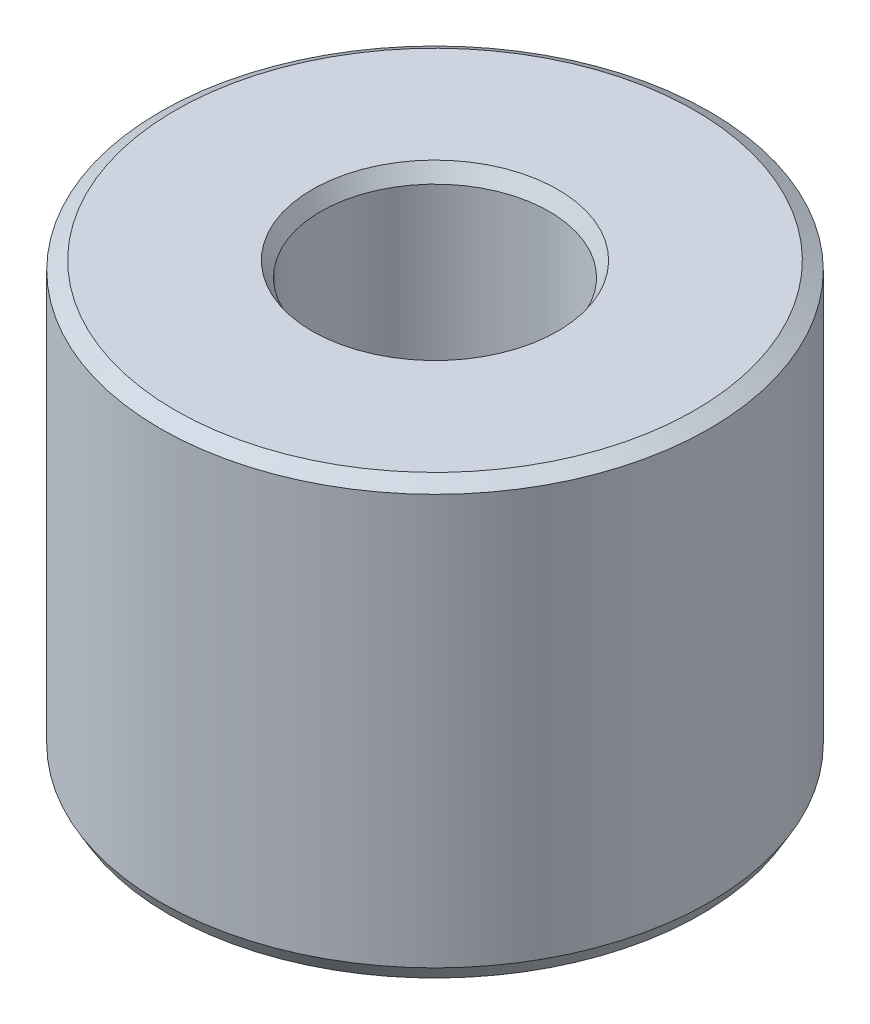
SolidWorks part; units mm, degrees
ref_plane "Front Plane" through (0, 0, 0) normal (0, 0, 1) x (1, 0, 0)
ref_plane "Top Plane" through (0, 0, 0) normal (0, 1, 0) x (1, 0, 0)
ref_plane "Right Plane" through (0, 0, 0) normal (1, 0, 0) x (0, 0, -1)
sketch "Sketch1" plane through (0, 0, 0) normal (0, 1, 0) x (1, 0, 0)
  circle A0 centre (0, 0) radius 40
  dimension "SLEEVE_OD" = 80
extrude "Boss-Extrude1" add sketch "Sketch1" along normal blind 63.1464
sketch "Sketch2" plane through (0, 0, 0) normal (0, 1, 0) x (1, 0, 0)
  circle A0 centre (0, 0) radius 16.6442
  dimension "BORE_D" = 33.2884
extrude "Cut-Extrude1" cut sketch "Sketch2" along normal through all
chamfer "Chamfer1" distance 1.244 angle 60 4 edges at (0, 63.1464, 16.6442) (0, 0, 16.6442) (0, 0, 40) (0, 63.1464, 40) first distance on face at (0, 63.1464, 16.6442) first distance on face at (0, 0, 16.6442) first distance on face at (0, 63.1464, 40)
